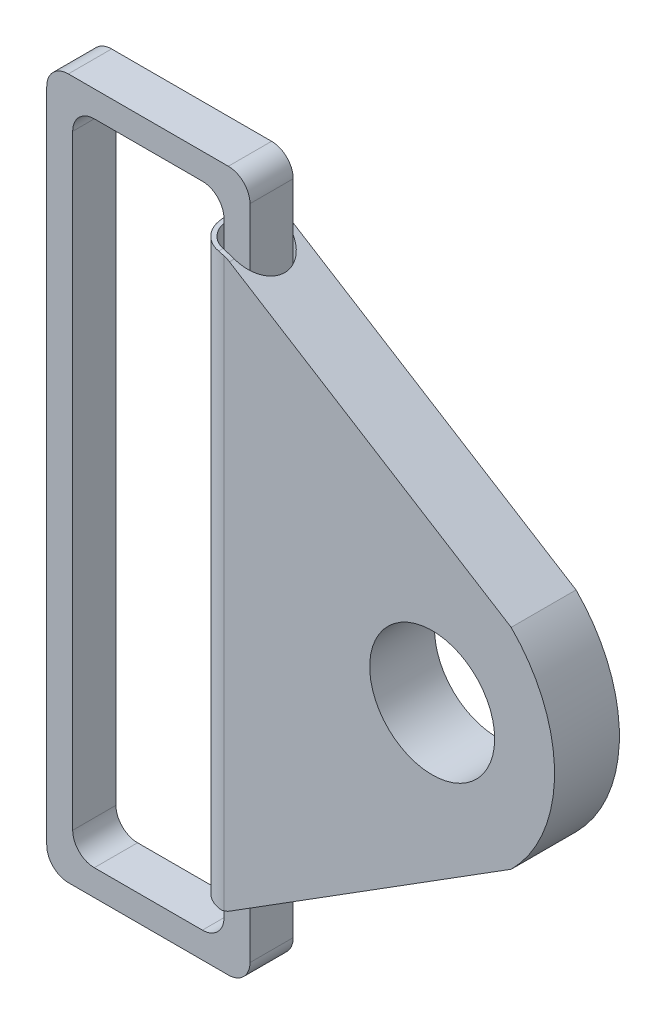
SolidWorks part; units mm, degrees
ref_plane "Piano frontale" through (0, 0, 0) normal (0, 0, 1) x (1, 0, 0)
ref_plane "Piano superiore" through (0, 0, 0) normal (0, 1, 0) x (1, 0, 0)
ref_plane "Piano destro" through (0, 0, 0) normal (1, 0, 0) x (0, 0, -1)
sketch "Schizzo1" plane through (0, 0, 0) normal (0, 0, 1) x (1, 0, 0)
  line L0 (0, 13.0495) -> (0, -13.2681)
  line L1 (0, -13.2681) -> (13.2739, -4.9218)
  line L2 (0, 13.0495) -> (13.2739, 4.7706)
  arc A0 (13.2739, -4.9218) -> (13.2739, 4.7706) centre (8.4277, -0.0756) ccw
  circle A1 centre (9.6206, -0.0756) radius 2.89
extrude "Estrusione-Estrusione1" add sketch "Schizzo1" along normal mid plane 3
sketch "Schizzo2" plane through (0, 0, 0) normal (0, 1, 0) x (1, 0, 0)
  circle A0 centre (0, 0) radius 1.5
extrude "Estrusione-Estrusione3" add sketch "Schizzo2" against normal up to surface and the other way up to surface up to face at (6.6369, -9.095, 0) other way up to face at (6.6369, 8.9101, 0)
sketch "Schizzo4" plane through (0, 0, 0) normal (0, 1, 0) x (1, 0, 0)
  circle A0 centre (0, 0) radius 1.2978
extrude "Taglio-Estrusione2" cut sketch "Schizzo4" against normal up to surface and the other way up to surface up to face at (6.2619, -9.3308, 0) other way up to face at (6.2619, 9.144, 0)
sketch "Schizzo5" plane through (0, 0, 0) normal (0, 0, 1) x (1, 0, 0)
  line L0 (0, 13.0495) -> (-1.5, 13.0495)
  line L1 (-1.5, 13.9851) -> (-1.5, -14.2113) construction
  line L2 (-1.5, 13.0495) -> (-1.5, 13.9851)
  line L3 (-1.5, 13.9851) -> (0, 13.0495)
  line L4 (0, -13.2681) -> (-1.5, -13.2681)
  line L5 (-1.5, -13.2681) -> (-1.5, -14.2113)
  line L6 (-1.5, -14.2113) -> (0, -13.2681)
extrude "Taglio-Estrusione3" cut sketch "Schizzo5" along normal through all both and the other way through all
fillet "Raccordo3" radius 1 2 edges at (0, 13.0495, -1.3989) (0, 13.0495, 1.3989)
fillet "Raccordo4" radius 1 2 edges at (0, -13.2681, -1.3989) (0, -13.2681, 1.3989)
sketch "Schizzo8" plane through (0, 0, 0) normal (0, 0, 1) x (1, 0, 0)
  line L5 (-0.5079, 15) -> (-0.5079, -15)
  line L6 (-0.5079, 15) -> (-7.5079, 15)
  line L7 (-0.5079, -15) -> (-7.5079, -15)
  line L8 (-7.5079, 15) -> (-7.5079, -15)
  dimension "D1" = 15
  dimension "D2" = 7
  dimension "D3" = 15
  dimension "D4" = 0.5079
extrude "Estrusione-Sottile1" add sketch "Schizzo8" along normal mid plane 2 separate body thin thin type one direction wall 1.2
fillet "Raccordo9" radius 1 4 edges at (0.6921, -16.2, 0) (-8.7079, -16.2, 0) (0.6921, 16.2, 0) (-8.7079, 16.2, 0) first distance on face at (-4.0079, -16.2, 0) first distance on face at (-4.0079, 16.2, 0)
fillet "Raccordo10" radius 1 4 edges at (-0.5079, -15, 0) (-7.5079, -15, 0) (-0.5079, 15, 0) (-7.5079, 15, 0) first distance on face at (-0.5079, 0, 0) first distance on face at (-7.5079, 0, 0)
